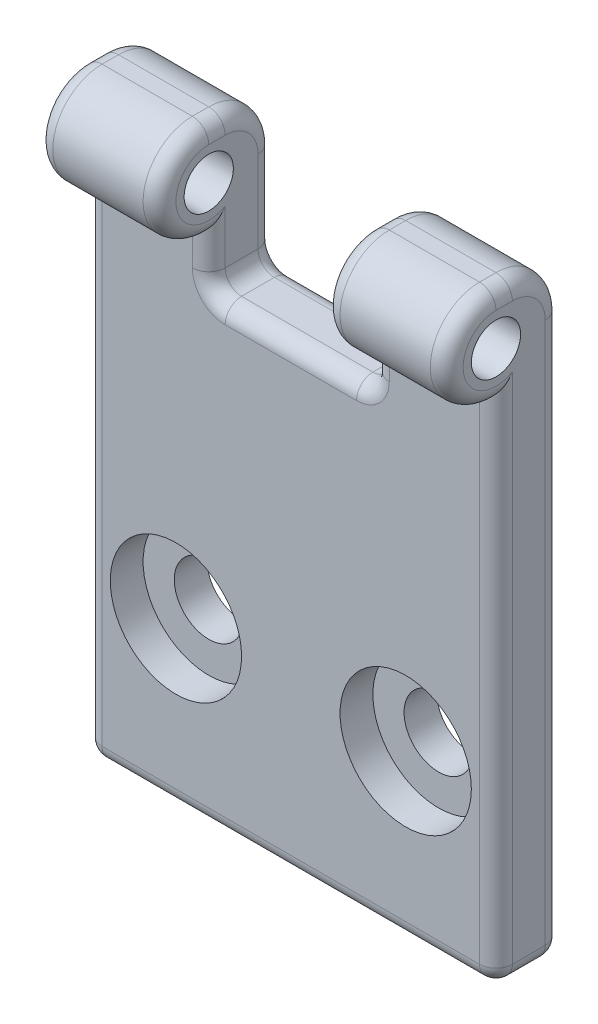
SolidWorks part; units mm, degrees
ref_plane "Plan de face" through (0, 0, 0) normal (0, 0, 1) x (1, 0, 0)
ref_plane "Plan de dessus" through (0, 0, 0) normal (0, 1, 0) x (1, 0, 0)
ref_plane "Plan de droite" through (0, 0, 0) normal (1, 0, 0) x (0, 0, -1)
sketch "Esquisse1" plane through (0, 0, 0) normal (0, 0, 1) x (1, 0, 0)
  line L1 (0, 0) -> (25, 0)
  line L2 (0, 0) -> (0, 37)
  line L3 (0, 37) -> (25, 37)
  line L4 (25, 0) -> (25, 37)
  dimension "D1" = 37
  dimension "D2" = 25
extrude "Boss.-Extru.1" add sketch "Esquisse1" along normal blind 4
sketch "Esquisse2" plane through (25, 0, 0) normal (1, 0, 0) x (0, 0, -1)
  line L0 (-4, 0) -> (-4, 37) construction
  circle A0 centre (-4, 34) radius 3
  dimension "D1" = 6
extrude "Boss.-Extru.2" add sketch "Esquisse2" against normal blind 25
sketch "Esquisse3" plane through (25, 0, 0) normal (1, 0, 0) x (0, 0, -1)
  line L4 (0, 37) -> (-4, 37)
  line L5 (-4, 31) -> (-4, 0)
  line L6 (-4, 0) -> (0, 0)
  line L7 (0, 0) -> (0, 37)
  line L8 (-3, 37) -> (-4, 37)
  line L9 (-4, 31) -> (-4, 0)
  line L10 (-4, 0) -> (0, 0)
  line L11 (0, 0) -> (0, 34)
  circle A0 centre (-4, 34) radius 1.5
  arc A1 (-4, 37) -> (-4, 31) centre (-4, 34) ccw
  arc A2 (-4, 37) -> (-4, 31) centre (-4, 34) ccw
  arc A3 (0, 34) -> (-3, 37) centre (-3, 34) ccw
  line M6 (0, 37) -> (-4, 37)
  line M10 (0, 0) -> (0, 37)
  dimension "D2" = 3
  dimension "D3" = 3
  dimension "D1" = 0
extrude "Enlèv. mat.-Extru.1" cut sketch "Esquisse3" against normal blind 25 contours A0 | A3 M10 M6 region at (25, 36.3299, 0.6701) region at (25, 34, 4)
sketch "Esquisse4" plane through (0, 0, 4) normal (0, 0, 1) x (1, 0, 0)
  line L0 (25, 37) -> (0, 37) construction
  line L1 (7.5, 25) -> (17.5, 25)
  line L2 (7.5, 25) -> (7.5, 37)
  line L3 (7.5, 37) -> (17.5, 37)
  line L4 (25, 0) -> (25, 31)
  line L5 (25, 31) -> (0, 31)
  line L6 (0, 31) -> (0, 0)
  line L7 (0, 0) -> (25, 0)
  line L8 (25, 0) -> (25, 31)
  line L9 (25, 31) -> (0, 31)
  line L10 (0, 31) -> (0, 0)
  line L11 (0, 0) -> (25, 0)
  line L12 (17.5, 25) -> (17.5, 37)
  line L13 (7.5, 25) -> (17.5, 37) construction
  line L14 (7.5, 37) -> (17.5, 25) construction
  line L15 (7.5, 28) -> (17.5, 28)
  point P2 (12.5, 31)
  point P13 (12.5, 28)
  dimension "D2" = 10
  dimension "D3" = 9
  dimension "D1" = 0
extrude "Enlèv. mat.-Extru.2" cut sketch "Esquisse4" against normal blind 25 and the other way blind 25 contours L9 L12 L3 L2 | L2 L15 L12 L9 region at (12.5, 29.5, 4) region at (12.5, 34, 4)
sketch "Esquisse5" plane through (0, 0, 4) normal (0, 0, 1) x (1, 0, 0)
  line L1 (0, 0) -> (25, 0)
  line L2 (0, 0) -> (0, 10)
  line L3 (0, 10) -> (25, 10)
  line L4 (25, 0) -> (25, 10)
  line L8 (17.5, 28) -> (7.5, 28)
  line L9 (7.5, 28) -> (7.5, 31)
  line L10 (7.5, 31) -> (0, 31)
  line L11 (0, 31) -> (0, 0)
  line L12 (0, 0) -> (25, 0)
  line L13 (25, 0) -> (25, 31)
  line L14 (25, 31) -> (17.5, 31)
  line L15 (17.5, 31) -> (17.5, 28)
  line L16 (17.5, 28) -> (7.5, 28)
  line L17 (7.5, 28) -> (7.5, 31)
  line L18 (7.5, 31) -> (0, 31)
  line L19 (0, 31) -> (0, 0)
  line L20 (0, 0) -> (25, 0)
  line L21 (25, 0) -> (25, 31)
  line L22 (25, 31) -> (17.5, 31)
  line L23 (17.5, 31) -> (17.5, 28)
  point P8 (5.5, 10)
  point P10 (19.5, 10)
  dimension "D2" = 10
  dimension "5.5" = 5.5
  dimension "D4" = 5.5
  dimension "D1" = 0
hole_wizard "Chambrage pour vis à six pans creux M41" positions "Esquisse3D2" profile "Esquisse7" counterbore size "M4" standard "ISO" end condition through all
sketch3d "Esquisse3D2"
  point P0 (5.5, 10, 4)
  point P3 (19.5, 10, 4)
sketch "Esquisse7" plane through (5.5, 10, 4) normal (1, 0, 0) x (0, -1, 0)
  line L0 (0, 0) -> (0, 4)
  line L1 (0, 4) -> (2.1, 4)
  line L3 (2.1, 4) -> (2.1, 2)
  line L4 (2.1, 2) -> (4, 2)
  line L5 (4, 2) -> (4, 0)
  line L7 (4, 0) -> (0, 0)
  line L11 (0, -6.35) -> (0, 107.95) construction
  dimension "Diamètre du perçage jusqu'au prochain" = 4.2
  dimension "Profondeur du perçage jusqu'au prochain" = 4
  dimension "Diamètre du chambrage" = 8
  dimension "Profondeur du chambrage" = 2
fillet "Congé1" radius 1 28 edges at (7.5, 34, 7) (17.5, 34, 7) (7.5, 37, 3.5) (17.5, 37, 3.5) (7.5, 36.1213, 0.8787) (17.5, 36.1213, 0.8787) (7.5, 29.5, 4) (7.5, 31, 0) (17.5, 29.5, 4) (17.5, 31, 0) (25, 34, 7) (25, 37, 3.5) (25, 36.1213, 0.8787) (0, 34, 7) (0, 37, 3.5) (0, 36.1213, 0.8787) (0, 0, 2) (12.5, 0, 4) (25, 0, 2) (12.5, 0, 0) (7.5, 28, 2) (17.5, 28, 2) (12.5, 28, 0) (12.5, 28, 4) (25, 15.5, 4) (25, 17, 0) (0, 15.5, 4) (0, 17, 0)
